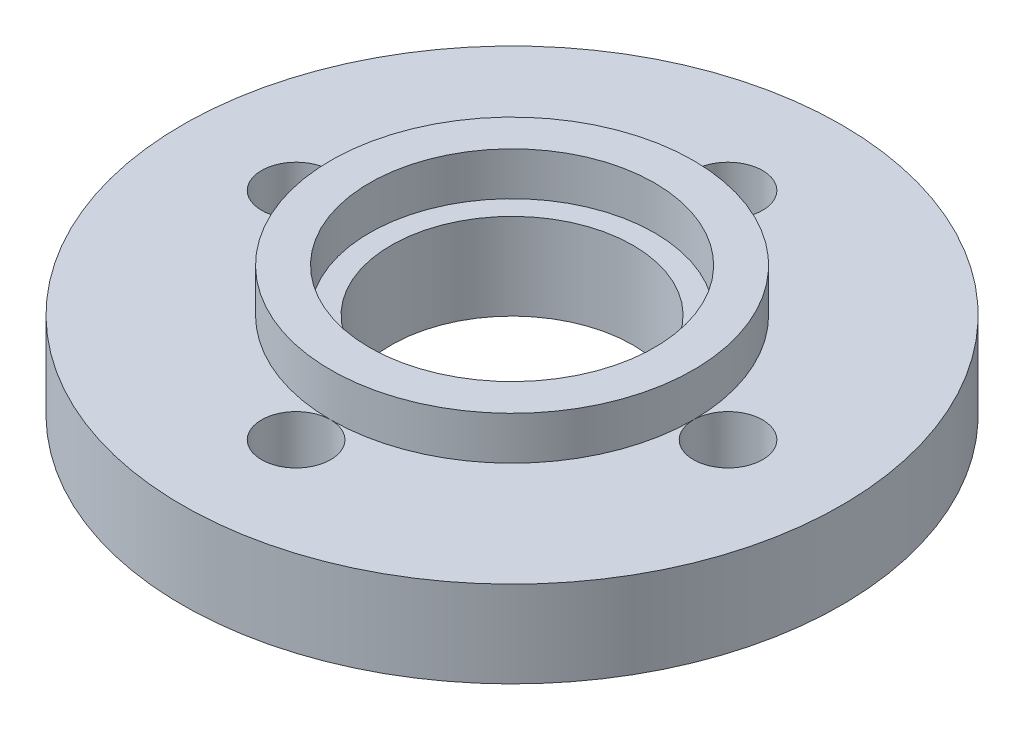
SolidWorks part; units mm, degrees
ref_plane "Спереди" through (0, 0, 0) normal (0, 0, 1) x (1, 0, 0)
ref_plane "Сверху" through (0, 0, 0) normal (0, 1, 0) x (1, 0, 0)
ref_plane "Справа" through (0, 0, 0) normal (1, 0, 0) x (0, 0, -1)
other "Configuration Table"
sketch "Sketch1" plane through (0, 0, 0) normal (0, 0, 1) x (1, 0, 0)
  line L0 (14, 0.2336) -> (38.1501, 0.2336)
  line L1 (38.1501, 0.2336) -> (38.1501, 10.2336)
  line L2 (38.1501, 10.2336) -> (21, 10.2336)
  line L3 (21, 10.2336) -> (21, 15.2336)
  line L4 (21, 15.2336) -> (16.5, 15.2336)
  line L5 (16.5, 15.2336) -> (16.5, 10.2336)
  line L6 (16.5, 10.2336) -> (14, 10.2336)
  line L7 (14, 10.2336) -> (14, 0.2336)
  line L8 (0, 0) -> (0, 36.6782) construction
  line L9 (-14, 10.2336) -> (-14, 0.2336)
  line L10 (-16.5, 10.2336) -> (-14, 10.2336)
  line L11 (-16.5, 15.2336) -> (-16.5, 10.2336)
  line L12 (-21, 15.2336) -> (-16.5, 15.2336)
  line L13 (-21, 10.2336) -> (-21, 15.2336)
  line L14 (-38.1501, 10.2336) -> (-21, 10.2336)
  line L15 (-38.1501, 0.2336) -> (-38.1501, 10.2336)
  line L16 (-14, 0.2336) -> (-38.1501, 0.2336)
  point P19 (21, 12.7336)
  point P20 (0, 0)
  dimension "D1" = 15
  dimension "D2" = 5
  dimension "D4" = 42
  dimension "D5" = 33
  dimension "D6" = 28
sketch "Sketch7" plane through (0, 0, 0) normal (0, 0, 1) x (1, 0, 0)
revolve "Revolve2" add sketch "Sketch1" angle 360 about L8
sketch "Sketch14" plane through (0, 10.2336, 0) normal (0, 1, 0) x (1, 0, 0)
  line L1 (-50, 0) -> (50, 0) construction
  circle A0 centre (25, 0) radius 4
  circle A1 centre (0, 25) radius 4
  circle A2 centre (0, 0) radius 25 construction
  circle A3 centre (-25, 0) radius 4
  circle A4 centre (0, -25) radius 4
  point P16 (0, 0)
  point P17 (0, 0)
  dimension "D1" = 8
  dimension "D2" = 50
  dimension "D3" = 4
extrude "Cut-Extrude2" cut sketch "Sketch14" against normal up to surface (10 mm away) up to face at (0, 0.2336, -38.1501)
